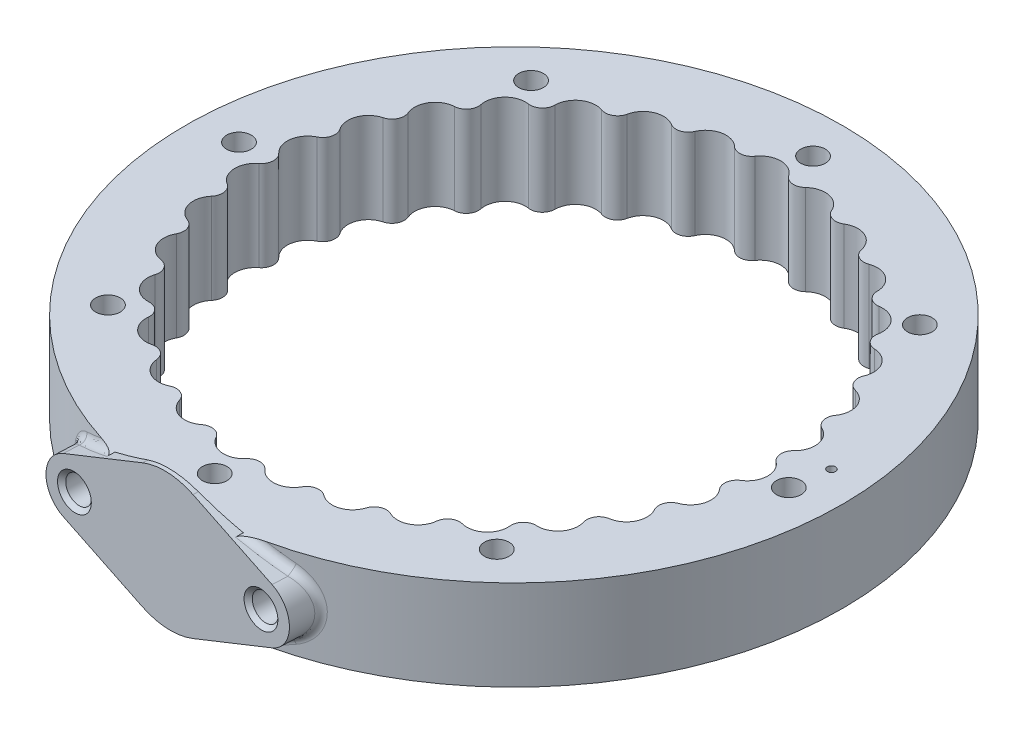
SolidWorks part; units mm, degrees
note: '?' marks a value the reader was unsure of.
ref_plane "Front Plane" through (0, 0, 0) normal (0, 0, 1) x (1, 0, 0)
ref_plane "Top Plane" through (0, 0, 0) normal (0, 1, 0) x (1, 0, 0)
ref_plane "Right Plane" through (0, 0, 0) normal (1, 0, 0) x (0, 0, -1)
sketch "Sketch1" plane through (0, 0, 0) normal (0, 1, 0) x (1, 0, 0)
  arc A0 (-38.2573, 46.221) -> (-39.8947, 44.8153) centre (0, 0) ccw
  arc A1 (4.9957, 59.7917) -> (-4.9957, 59.7917) centre (0, 60) ccw
  arc A2 (16.9294, 57.5621) -> (7.1426, 59.5733) centre (12.0779, 58.7718) ccw
  arc A3 (28.17, 52.976) -> (18.9884, 56.9161) centre (23.6614, 55.1375) ccw
  arc A4 (38.2573, 46.221) -> (30.0568, 51.9287) centre (34.2761, 49.2458) ccw
  arc A5 (46.7784, 37.5737) -> (39.8947, 44.8153) centre (43.4876, 41.338) ccw
  arc A6 (53.3844, 27.3881) -> (48.0993, 35.8672) centre (50.9187, 31.7378) ccw
  arc A7 (57.8048, 16.0813) -> (54.3347, 25.4506) centre (56.2651, 20.8383) ccw
  arc A8 (59.8586, 4.1161) -> (58.3457, 13.9922) centre (59.3081, 9.0857) ccw
  arc A9 (59.4619, -8.0176) -> (59.968, 1.9608) centre (59.923, -3.039) ccw
  arc A10 (56.6308, -19.8231) -> (59.1351, -10.1508) centre (58.0846, -15.0392) ccw
  arc A11 (51.4812, -30.817) -> (55.8813, -21.8468) centre (53.8683, -26.4236) ccw
  arc A12 (44.2239, -40.5493) -> (50.3397, -32.6484) centre (47.4465, -36.7264) ccw
  arc A13 (35.1562, -48.6214) -> (42.7371, -42.1134) centre (39.0823, -45.5255) ccw
  arc A14 (24.6491, -54.703) -> (33.3849, -49.8542) centre (29.1181, -52.4608) ccw
  arc A15 (13.1329, -58.5451) -> (22.666, -55.5541) centre (17.9618, -57.2484) ccw
  arc A16 (1.079, -59.9903) -> (11.019, -58.9795) centre (6.0701, -59.6922) ccw
  arc A17 (-11.019, -58.9795) -> (-1.079, -59.9903) centre (-6.0701, -59.6922) ccw
  arc A18 (-22.666, -55.5541) -> (-13.1329, -58.5451) centre (-17.9618, -57.2484) ccw
  arc A19 (-33.3849, -49.8542) -> (-24.6491, -54.703) centre (-29.1181, -52.4608) ccw
  arc A20 (-42.7371, -42.1134) -> (-35.1562, -48.6214) centre (-39.0823, -45.5255) ccw
  arc A21 (-50.3397, -32.6484) -> (-44.2239, -40.5493) centre (-47.4465, -36.7264) ccw
  arc A22 (-55.8813, -21.8468) -> (-51.4812, -30.817) centre (-53.8683, -26.4236) ccw
  arc A23 (-59.1351, -10.1508) -> (-56.6308, -19.8231) centre (-58.0846, -15.0392) ccw
  arc A24 (-59.968, 1.9608) -> (-59.4619, -8.0176) centre (-59.923, -3.039) ccw
  arc A25 (-58.3457, 13.9922) -> (-59.8586, 4.1161) centre (-59.3081, 9.0857) ccw
  arc A26 (-54.3347, 25.4506) -> (-57.8048, 16.0813) centre (-56.2651, 20.8383) ccw
  arc A27 (-48.0993, 35.8672) -> (-53.3844, 27.3881) centre (-50.9187, 31.7378) ccw
  arc A28 (-39.8947, 44.8153) -> (-46.7784, 37.5737) centre (-43.4876, 41.338) ccw
  arc A29 (-30.0568, 51.9287) -> (-38.2573, 46.221) centre (-34.2761, 49.2458) ccw
  arc A30 (-18.9884, 56.9161) -> (-28.17, 52.976) centre (-23.6614, 55.1375) ccw
  arc A31 (-7.1426, 59.5733) -> (-16.9294, 57.5621) centre (-12.0779, 58.7718) ccw
  circle A32 centre (0, 0) radius 80
  arc A33 (-46.7784, 37.5737) -> (-48.0993, 35.8672) centre (0, 0) ccw
  arc A34 (-53.3844, 27.3881) -> (-54.3347, 25.4506) centre (0, 0) ccw
  arc A35 (-57.8048, 16.0813) -> (-58.3457, 13.9922) centre (0, 0) ccw
  arc A36 (-59.8586, 4.1161) -> (-59.968, 1.9608) centre (0, 0) ccw
  arc A37 (-59.4619, -8.0176) -> (-59.1351, -10.1508) centre (0, 0) ccw
  arc A38 (-56.6308, -19.8231) -> (-55.8813, -21.8468) centre (0, 0) ccw
  arc A39 (-51.4812, -30.817) -> (-50.3397, -32.6484) centre (0, 0) ccw
  arc A40 (-44.2239, -40.5493) -> (-42.7371, -42.1134) centre (0, 0) ccw
  arc A41 (-35.1562, -48.6214) -> (-33.3849, -49.8542) centre (0, 0) ccw
  arc A42 (-24.6491, -54.703) -> (-22.666, -55.5541) centre (0, 0) ccw
  arc A43 (-13.1329, -58.5451) -> (-11.019, -58.9795) centre (0, 0) ccw
  arc A44 (11.019, -58.9795) -> (13.1329, -58.5451) centre (0, 0) ccw
  arc A45 (-1.079, -59.9903) -> (1.079, -59.9903) centre (0, 0) ccw
  arc A46 (22.666, -55.5541) -> (24.6491, -54.703) centre (0, 0) ccw
  arc A47 (33.3849, -49.8542) -> (35.1562, -48.6214) centre (0, 0) ccw
  arc A48 (42.7371, -42.1134) -> (44.2239, -40.5493) centre (0, 0) ccw
  arc A49 (50.3397, -32.6484) -> (51.4812, -30.817) centre (0, 0) ccw
  arc A50 (55.8813, -21.8468) -> (56.6308, -19.8231) centre (0, 0) ccw
  arc A51 (59.1351, -10.1508) -> (59.4619, -8.0176) centre (0, 0) ccw
  arc A52 (59.968, 1.9608) -> (59.8586, 4.1161) centre (0, 0) ccw
  arc A53 (58.3457, 13.9922) -> (57.8048, 16.0813) centre (0, 0) ccw
  arc A54 (54.3347, 25.4506) -> (53.3844, 27.3881) centre (0, 0) ccw
  arc A55 (48.0993, 35.8672) -> (46.7784, 37.5737) centre (0, 0) ccw
  arc A56 (39.8947, 44.8153) -> (38.2573, 46.221) centre (0, 0) ccw
  arc A57 (30.0568, 51.9287) -> (28.17, 52.976) centre (0, 0) ccw
  arc A58 (18.9884, 56.9161) -> (16.9294, 57.5621) centre (0, 0) ccw
  arc A59 (7.1426, 59.5733) -> (4.9957, 59.7917) centre (0, 0) ccw
  arc A60 (-4.9957, 59.7917) -> (-7.1426, 59.5733) centre (0, 0) ccw
  arc A61 (-16.9294, 57.5621) -> (-18.9884, 56.9161) centre (0, 0) ccw
  arc A62 (-28.17, 52.976) -> (-30.0568, 51.9287) centre (0, 0) ccw
  dimension "D1" = 120
  dimension "D2" = 10
  dimension "D4" = 160
  dimension "D3" = 31
extrude "Boss-Extrude1" add sketch "Sketch1" along normal blind 22
fillet "Fillet1" radius 2.5 62 edges at (44.2239, 11, 40.5493) (42.7371, 11, 42.1134) (35.1562, 11, 48.6214) (33.3849, 11, 49.8542) (24.6491, 11, 54.703) (22.666, 11, 55.5541) (13.1329, 11, 58.5451) (11.019, 11, 58.9795) (1.079, 11, 59.9903) (-1.079, 11, 59.9903) (-11.019, 11, 58.9795) (-13.1329, 11, 58.5451) (-22.666, 11, 55.5541) (-24.6491, 11, 54.703) (-33.3849, 11, 49.8542) (-35.1562, 11, 48.6214) (-42.7371, 11, 42.1134) (-44.2239, 11, 40.5493) (-50.3397, 11, 32.6484) (-51.4812, 11, 30.817) (-55.8813, 11, 21.8468) (-56.6308, 11, 19.8231) (-59.1351, 11, 10.1508) (-59.4619, 11, 8.0176) (-59.968, 11, -1.9608) (-59.8586, 11, -4.1161) (-58.3457, 11, -13.9922) (-57.8048, 11, -16.0813) (-54.3347, 11, -25.4506) (-53.3844, 11, -27.3881) (50.3397, 11, 32.6484) (51.4812, 11, 30.817) (55.8813, 11, 21.8468) (56.6308, 11, 19.8231) (59.1351, 11, 10.1508) (59.4619, 11, 8.0176) (59.968, 11, -1.9608) (59.8586, 11, -4.1161) (58.3457, 11, -13.9922) (57.8048, 11, -16.0813) (54.3347, 11, -25.4506) (53.3844, 11, -27.3881) (48.0993, 11, -35.8672) (46.7784, 11, -37.5737) (38.2573, 11, -46.221) (39.8947, 11, -44.8153) (30.0568, 11, -51.9287) (28.17, 11, -52.976) (18.9884, 11, -56.9161) (16.9294, 11, -57.5621) (7.1426, 11, -59.5733) (4.9957, 11, -59.7917) (-4.9957, 11, -59.7917) (-7.1426, 11, -59.5733) (-16.9294, 11, -57.5621) (-18.9884, 11, -56.9161) (-28.17, 11, -52.976) (-30.0568, 11, -51.9287) (-38.2573, 11, -46.221) (-39.8947, 11, -44.8153) (-46.7784, 11, -37.5737) (-48.0993, 11, -35.8672)
fillet "Fillet2" radius 3 31 edges at (60.0791, 11, -3.0469) (59.4626, 11, 9.1093) (56.4117, 11, 20.8926) (51.0513, 11, 31.8205) (43.6009, 11, 41.4457) (34.3654, 11, 49.3741) (23.723, 11, 55.2812) (12.1094, 11, 58.9249) (0, 11, 60.1564) (-12.1094, 11, 58.9249) (-23.723, 11, 55.2812) (-34.3654, 11, 49.3741) (-43.6009, 11, 41.4457) (-51.0513, 11, 31.8205) (-56.4117, 11, 20.8926) (-59.4626, 11, 9.1093) (-60.0791, 11, -3.0469) (-58.236, 11, -15.0783) (-54.0086, 11, -26.4925) (58.236, 11, -15.0783) (54.0086, 11, -26.4925) (47.5702, 11, -36.8221) (39.1842, 11, -45.6441) (29.194, 11, -52.5975) (18.0086, 11, -57.3975) (6.0859, 11, -59.8477) (-6.0859, 11, -59.8477) (-18.0086, 11, -57.3975) (-29.194, 11, -52.5975) (-39.1842, 11, -45.6441) (-47.5702, 11, -36.8221)
sketch "Sketch3" plane through (0, 22, 0) normal (0, 1, 0) x (1, 0, 0)
  circle A0 centre (0, 0) radius 70 construction
  circle A1 centre (69.9376, -2.9549) radius 3
  circle A2 centre (47.3639, -51.5428) radius 3
  circle A3 centre (-2.9549, -69.9376) radius 3
  circle A4 centre (-51.5428, -47.3639) radius 3
  circle A5 centre (-69.9376, 2.9549) radius 3
  circle A6 centre (-47.3639, 51.5428) radius 3
  circle A7 centre (2.9549, 69.9376) radius 3
  circle A8 centre (51.5428, 47.3639) radius 3
  point P17 (0, 0)
  dimension "D1" = 140
  dimension "D2" = 6
  dimension "D4" = 2.9549
  dimension "D3" = 8
extrude "Cut-Extrude1" cut sketch "Sketch3" against normal through all
sketch "Sketch5" plane through (0, 22, 0) normal (0, 1, 0) x (1, 0, 0)
  circle A0 centre (71.247, 6.1342) radius 1
  dimension "D1" = 2
extrude "Cut-Extrude3" cut sketch "Sketch5" against normal blind 2
ref_axis "Axis1" through (69.9376, 0, 2.9549) along (0, 1, 0)?
ref_axis "Axis2" through (-69.9376, 0, -2.9549) along (0, 1, 0)?
ref_plane "Plane1" through (0, 0, 0) normal (0.0422, 0, -0.9991) x (-0.9991, 0, -0.0422)
ref_plane "Plane2" through (-3.3771, 0, 79.9287) normal (-0.0422, 0, 0.9991) x (0.9991, 0, 0.0422)
ref_plane "Plane3" through (-3.4193, 0, 80.9278) normal (-0.0422, 0, 0.9991) x (0.9991, 0, 0.0422)
sketch "Sketch6" plane through (-3.4193, 0, 80.9278) normal (-0.0422, 0, 0.9991) x (0.9991, 0, 0.0422)
  line L0 (-26.5737, 17.6775) -> (-6.4263, 26.1971)
  line L1 (6.4263, 26.1971) -> (26.5737, 17.6775)
  line L2 (-26.5737, 4.3225) -> (-6.4263, -4.1971)
  line L3 (6.4263, -4.1971) -> (26.5737, 4.3225)
  line L4 (-80, 0) -> (80, 0) construction
  arc A0 (-6.4263, -4.1971) -> (6.4263, -4.1971) centre (0, 11) ccw
  arc A1 (26.5737, 4.3225) -> (26.5737, 17.6775) centre (23.75, 11) ccw
  arc A2 (-26.5737, 17.6775) -> (-26.5737, 4.3225) centre (-23.75, 11) ccw
  arc A3 (6.4263, 26.1971) -> (-6.4263, 26.1971) centre (0, 11) ccw
  dimension "D1" = 33
  dimension "D2" = 23.75
  dimension "D3" = 23.75
  dimension "D4" = 11
extrude "Boss-Extrude2" add sketch "Sketch6" against normal up to surface (1.2585 mm away)
sketch "Sketch7" plane through (-3.4193, 0, 80.9278) normal (-0.0422, 0, 0.9991) x (0.9991, 0, 0.0422)
  circle A0 centre (-23.75, 11) radius 3.3
  circle A1 centre (23.75, 11) radius 3.3
  dimension "D1" = 6.6
extrude "Cut-Extrude4" cut sketch "Sketch7" against normal blind 10.5
chamfer "Chamfer1" distance 1 angle 45 2 edges at (-23.8511, 11, 80.0645) (23.6066, 11, 82.0697)
fillet "Fillet3" radius 2 6 edges at (18.2382, 2.1813, 77.8933) (18.2382, 19.8187, 77.8933) (-24.7436, 19.8187, 76.0773) (-24.7436, 2.1813, 76.0773) (27.798, 10.0678, 75.0152) (-34.0265, 11.9322, 72.403)
equation "\"R_ROLL\"= 5mm"
equation "\"D_SUN\"= 120mm"
equation "\"NUM_ROLL\"= 31"
equation "\"RHO\"= 1mm"
equation "\"D_SHAFT\"= 20mm"
equation "\"D_OUTPUT\"= 80mm"
equation "\"NUM_OUT\"= 8"
equation "\"R_OUT_ROLL\"= 5mm"
equation "\"D1@Sketch1\"=\"D_SUN\""
equation "\"D2@Sketch1\"=\"R_ROLL\"*2"
equation "\"D3@Sketch1\"=\"NUM_ROLL\""
equation "\"a\"= \"D_SUN\" + 30"
equation "\"D4@Sketch1\"=\"D_SUN\"+40"
